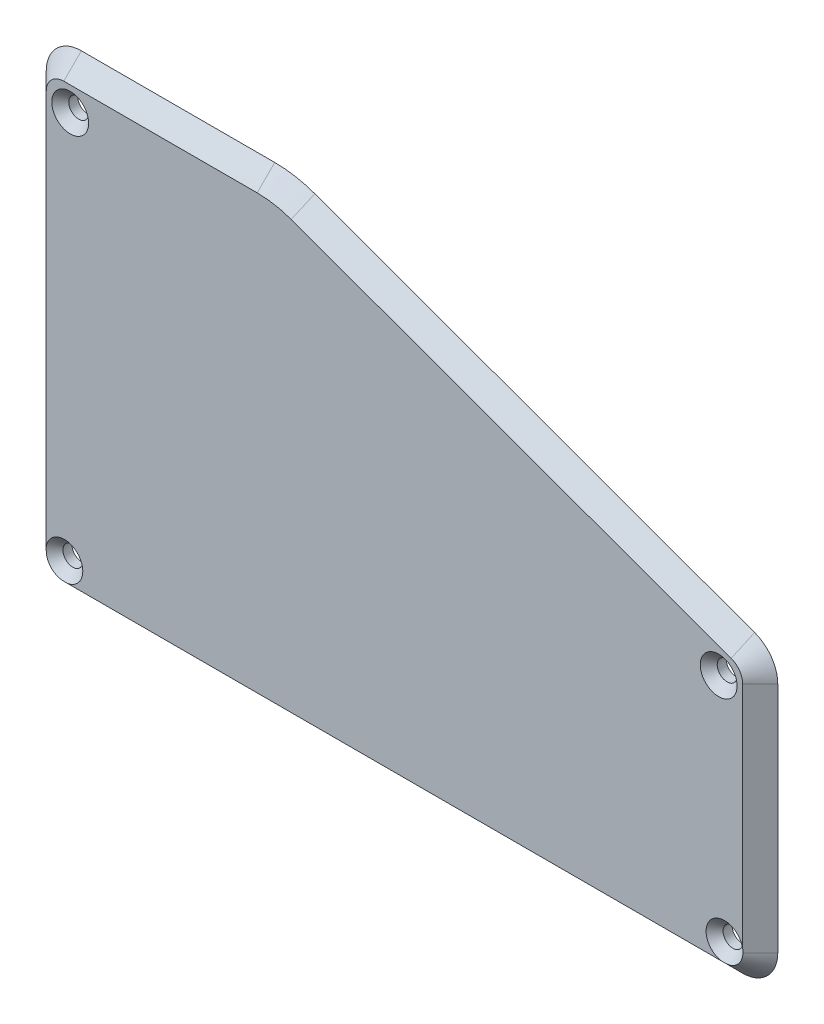
SolidWorks part; units mm, degrees
ref_plane "Спереди" through (0, 0, 0) normal (0, 0, 1) x (1, 0, 0)
ref_plane "Сверху" through (0, 0, 0) normal (0, 1, 0) x (1, 0, 0)
ref_plane "Справа" through (0, 0, 0) normal (1, 0, 0) x (0, 0, -1)
sketch "Эскиз1" plane through (0, 0, 0) normal (0, 0, 1) x (1, 0, 0)
  line L0 (56.5, 0) -> (-56.5, 0) construction
  line L1 (-62.5, 6) -> (-62.5, 74) construction
  line L2 (-56.5, 80) -> (-23.4509, 80) construction
  line L3 (-16.6105, 78.7939) -> (58.5521, 51.4369) construction
  line L4 (62.5, 45.7988) -> (62.5, 6) construction
  line L20 (56.5, 0) -> (-56.5, 0)
  line L21 (-62.5, 6) -> (-62.5, 74)
  line L22 (-56.5, 80) -> (-23.4509, 80)
  line L23 (-16.6105, 78.7939) -> (58.5521, 51.4369)
  line L24 (62.5, 45.7988) -> (62.5, 6)
  arc A0 (-62.5, 6) -> (-56.5, 0) centre (-56.5, 6) ccw construction
  arc A1 (-56.5, 80) -> (-62.5, 74) centre (-56.5, 74) ccw construction
  arc A2 (-16.6105, 78.7939) -> (-23.4509, 80) centre (-23.4509, 60) ccw construction
  arc A3 (62.5, 45.7988) -> (58.5521, 51.4369) centre (56.5, 45.7988) ccw construction
  arc A4 (56.5, 0) -> (62.5, 6) centre (56.5, 6) ccw construction
  arc A5 (-62.5, 6) -> (-56.5, 0) centre (-56.5, 6) ccw
  arc A6 (-56.5, 80) -> (-62.5, 74) centre (-56.5, 74) ccw
  arc A7 (-16.6105, 78.7939) -> (-23.4509, 80) centre (-23.4509, 60) ccw
  arc A8 (62.5, 45.7988) -> (58.5521, 51.4369) centre (56.5, 45.7988) ccw
  arc A9 (56.5, 0) -> (62.5, 6) centre (56.5, 6) ccw
extrude "Бобышка-Вытянуть1" add sketch "Эскиз1" along normal blind 3
hole_wizard "Зенковка для винта с потайной головкой M31" positions "Эскиз4" profile "Эскиз5" countersink size "M3" standard "DIN" end condition through all
sketch "Эскиз4" plane through (0, 0, 3) normal (0, 0, 1) x (1, 0, 0)
  point P0 (-55.4, 72.9)
  point P3 (-56.4, 6.1)
  point P7 (55.4, 45.0285)
  point P10 (56.4, 6.1)
sketch "Эскиз5" plane through (-55.4, 72.9, 3) normal (1, 0, 0) x (0, -1, 0)
  line L0 (0, 0) -> (0, 3)
  line L1 (0, 3) -> (1.7, 3)
  line L2 (1.7, 3) -> (1.7, 1.45)
  line L3 (1.7, 1.45) -> (3.15, 0)
  line L5 (3.15, 0) -> (0, 0)
  line L6 (-1.7, 1.45) -> (-3.15, 0) construction
  line L11 (0, -6.35) -> (0, 107.95) construction
  dimension "Диаметр сквозного отверстия" = 3.4
  dimension "Глубина сквозного отверстия" = 3
  dimension "Диаметр передней зенковки" = 6.3
  dimension "Угол передней зенковки" = 90
chamfer "Фаска1" distance 3 angle 45 10 edges at (-60.7426, 1.7574, 3) (0, 0, 3) (-62.5, 40, 3) (60.7426, 1.7574, 3) (-60.7426, 78.2426, 3) (62.5, 25.8994, 3) (-39.9754, 80, 3) (61.4149, 49.2402, 3) (-19.9779, 79.6962, 3) (20.9708, 65.1154, 3)
